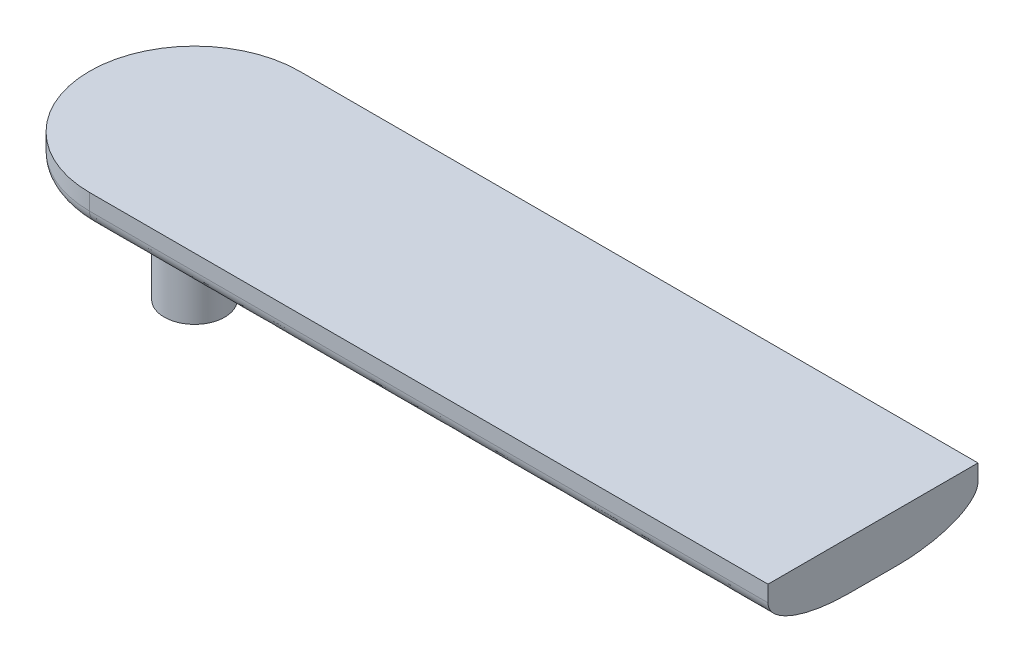
SolidWorks part; units mm, degrees
ref_plane "Front Plane" through (0, 0, 0) normal (0, 0, 1) x (1, 0, 0)
ref_plane "Top Plane" through (0, 0, 0) normal (0, 1, 0) x (1, 0, 0)
ref_plane "Right Plane" through (0, 0, 0) normal (1, 0, 0) x (0, 0, -1)
sketch "Sketch1" plane through (0, 0, 0) normal (0, 1, 0) x (1, 0, 0)
  line L1 (0, 6.5) -> (42, 6.5)
  line L2 (0, 6.5) -> (0, -6.5) construction
  line L3 (0, -6.5) -> (42, -6.5)
  line L4 (42, 6.5) -> (42, -6.5)
  arc A0 (0, 6.5) -> (0, -6.5) centre (0, 0) ccw
  arc A1 (0, -6.5) -> (0, 6.5) centre (0, 0) ccw construction
  dimension "D1" = 13
  dimension "D2" = 42
extrude "Boss-Extrude1" add sketch "Sketch1" along normal blind 3
fillet "Fillet1" radius 5 3 edges at (21, 0, -6.5) (-6.5, 0, 0) (21, 0, 6.5) second distance 2 first distance on face at (19.375, 0, 0)
sketch "Sketch2" plane through (0, 3, 0) normal (0, 1, 0) x (1, 0, 0)
  circle A0 centre (0, 0) radius 0.875
  circle A2 centre (0, 0) radius 1.875
  dimension "D1" = 1.75
  dimension "D2" = 1
extrude "Boss-Extrude3" add sketch "Sketch2" along a picked direction on the side against the normal offset from surface (9 mm away) 6 contours A2 A0
sketch "Sketch4" plane through (0, 3, 0) normal (0, 1, 0) x (1, 0, 0)
  circle A0 centre (0, 0) radius 0.875
  circle A1 centre (0, 0) radius 0.875 construction
extrude "Cut-Extrude2" cut sketch "Sketch4" against normal through all from offset 0.5 offset against normal yes
